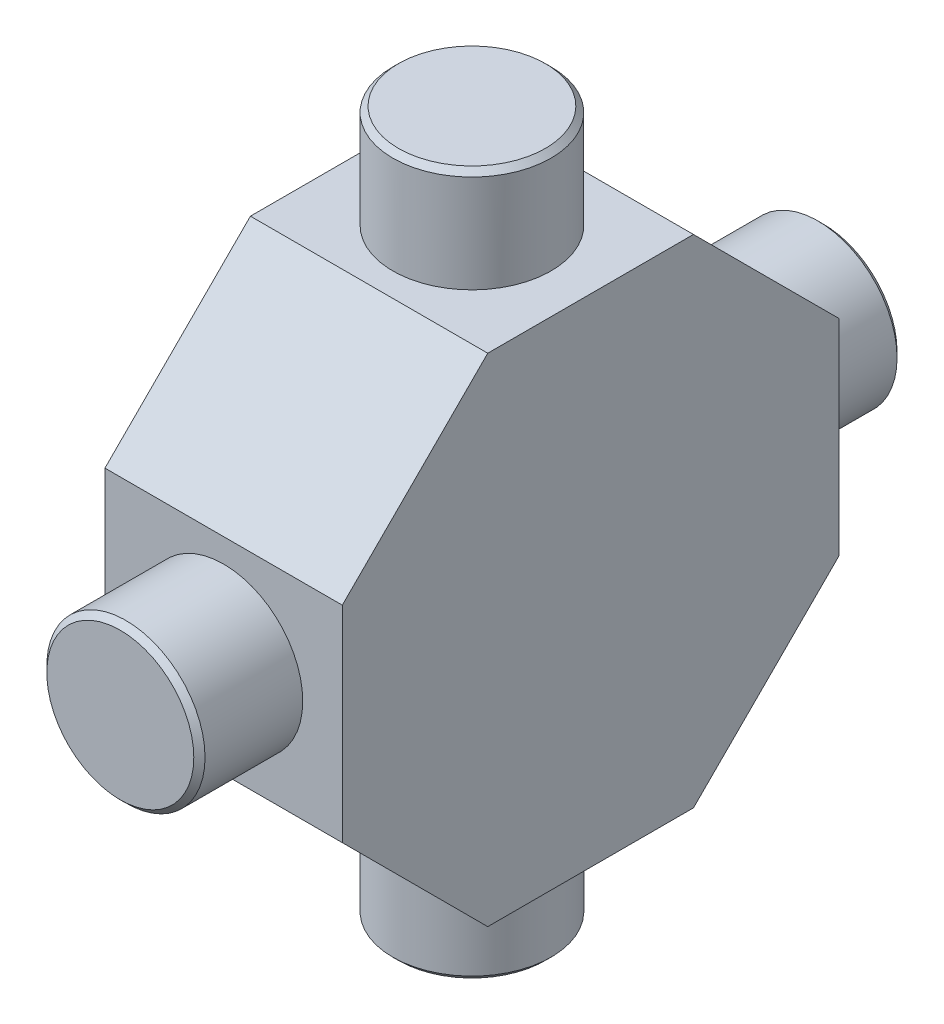
SolidWorks part; units mm, degrees
ref_plane "Front Plane" through (0, 0, 0) normal (0, 0, 1) x (1, 0, 0)
ref_plane "Top Plane" through (0, 0, 0) normal (0, 1, 0) x (1, 0, 0)
ref_plane "Right Plane" through (0, 0, 0) normal (1, 0, 0) x (0, 0, -1)
sketch "Sketch0" plane through (0, 0, 0) normal (0, 1, 0) x (1, 0, 0)
  line L0 (-63.5, 0) -> (63.5, 0) construction
  line L1 (-63.5, 20.6375) -> (-63.5, -20.6375) construction
  line L2 (-32.9406, 9.525) -> (-32.9406, -9.525) construction
  line L3 (-32.9406, 9.525) -> (-23.4156, 0) construction
  line L4 (-23.4156, 0) -> (-32.9406, -9.525) construction
  line L5 (-28.1781, 4.7625) -> (-28.1781, -4.7625) construction
  line L6 (0, 31.75) -> (0, -31.75) construction
  point P7 (-32.9406, 0)
  point P8 (0, 0)
  point P12 (-28.1781, 0)
  dimension "Overall Width" = 63.5
  dimension "Shaft Dia" = 19.05
sketch "Sketch1" plane through (0, 0, 0) normal (0, 1, 0) x (1, 0, 0)
  line L0 (-63.5, 20.6375) -> (-32.9406, 20.6375)
  line L2 (-32.9406, 0) -> (-63.5, 0)
  line L3 (-63.5, 0) -> (-63.5, 20.6375)
  line L4 (-63.5, 20.6375) -> (-63.5, -20.6375) construction
  line L5 (-63.5, 0) -> (63.5, 0) construction
  line L9 (-32.9406, 20.6375) -> (-32.9406, 0)
  line L11 (0, 0) -> (20.6375, 0) construction
  line L14 (0, 31.75) -> (0, 0) construction
  circle A0 centre (0, 0) radius 20.6375 construction
sketch "Sketch30" plane through (0, 0, 0) normal (0, 1, 0) x (1, 0, 0)
  line L0 (-39.2906, 21.6694) -> (-39.2906, -21.6694)
  line L1 (-39.2906, -21.6694) -> (-21.8281, -21.6694)
  line L2 (-39.2906, 21.6694) -> (-21.8281, 21.6694)
  line L3 (0, 14.2875) -> (-25.0022, 14.2875) construction
  line L4 (0, -14.2875) -> (-25.0022, -14.2875) construction
  line L5 (-21.8281, 21.6694) -> (14.2875, 21.6694)
  line L6 (14.2875, 21.6694) -> (14.2875, -21.6694)
  line L7 (-21.8281, -21.6694) -> (14.2875, -21.6694)
  line L8 (0, 31.75) -> (0, -31.75) construction
  line L9 (9.525, 0) -> (14.2875, 0) construction
  circle A0 centre (0, 0) radius 9.525 construction
  arc A2 (0, -14.2875) -> (0, 14.2875) centre (0, 0) ccw construction
  arc A3 (0, 14.2875) -> (-21.8281, 21.6694) centre (0, 50.2512) cw construction
  arc A4 (0, -14.2875) -> (-21.8281, -21.6694) centre (0, -50.2512) ccw construction
  circle A5 centre (0, 0) radius 14.2875 construction
  point P5 (12.388, 3.7874)
  dimension "D2" = 19.05
  dimension "D1" = 43.3388
  dimension "D3" = 4.7625
  dimension "D4" = 6.35
  dimension "D5" = 17.4625
sketch "Sketch6" plane through (0, 0, 0) normal (0, 1, 0) x (1, 0, 0)
  line L0 (-63.5, 0) -> (63.5, 0) construction
  line L1 (14.2875, 0) -> (7.1437, 0) construction
  line L2 (7.1437, 0) -> (0, 0) construction
  line L3 (14.2875, 21.6694) -> (14.2875, -21.6694) construction
  circle A0 centre (0, 0) radius 7.1437
  dimension "D1" = 14.2875
sketch "Sketch10" plane through (0, 0, 0) normal (0, 0, 1) x (1, 0, 0)
  circle A2 centre (0, 0) radius 7.1438
  point P1 (9.8548, 43.5315)
  dimension "D1" = 14.2875
extrude "Extrude10" add sketch "Sketch10" along normal blind 31.75 and the other way blind 31.75 separate body
sketch "Sketch31" plane through (0, 0, 0) normal (0, 1, 0) x (1, 0, 0)
  circle A2 centre (0, 0) radius 7.1438
  dimension "D1" = 14.2875
extrude "Boss-Extrude7" add sketch "Sketch31" against normal blind 31.75 and the other way blind 31.75 separate body
sketch "Sketch32" plane through (0, 0, 0) normal (1, 0, 0) x (0, 0, -1)
  line L11 (9.2869, -22.4205) -> (22.4205, -9.2869)
  line L12 (22.4205, -9.2869) -> (22.4205, 9.2869)
  line L13 (22.4205, 9.2869) -> (9.2869, 22.4205)
  line L16 (9.2869, 22.4205) -> (-9.2869, 22.4205)
  line L17 (-9.2869, 22.4205) -> (-22.4205, 9.2869)
  line L18 (-22.4205, 9.2869) -> (-22.4205, -9.2869)
  line L19 (-22.4205, -9.2869) -> (-9.2869, -22.4205)
  line L20 (-9.2869, -22.4205) -> (9.2869, -22.4205)
  circle A0 centre (0, 0) radius 22.4205 construction
  dimension "D2" = 18.5737
extrude "Boss-Extrude8" add sketch "Sketch32" along normal mid plane 21.4312
chamfer "Chamfer2" distance 0.508 angle 45 4 edges at (0, -31.75, 7.1438) (7.1438, 0, -31.75) (0, 31.75, 7.1438) (7.1438, 0, 31.75)
equation "\"D2@Sketch3\" = \"D1@Sketch3\" / 4"
equation "\"D1@Sketch30\" = \"OD@Sketch0\"*1.05"
equation "\"D2@Sketch32\" = \"D1@Sketch10\"*1.3"
equation "\"D1@Boss-Extrude8\" = \"D1@Sketch10\"*1.5"
